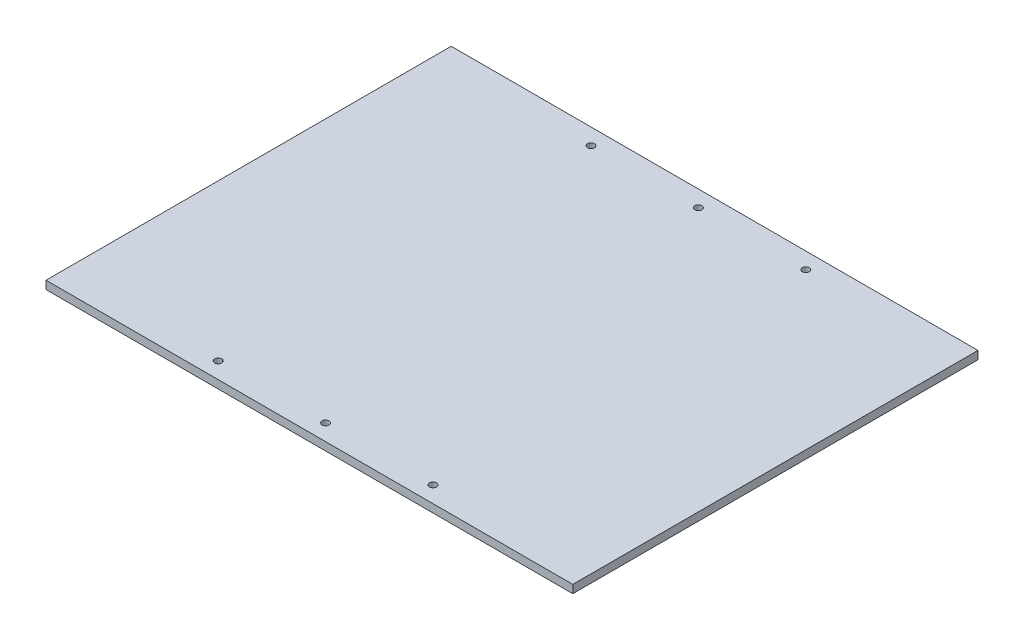
SolidWorks part; units mm, degrees
ref_plane "Ebene vorne" through (0, 0, 0) normal (0, 0, 1) x (1, 0, 0)
ref_plane "Ebene oben" through (0, 0, 0) normal (0, 1, 0) x (1, 0, 0)
ref_plane "Ebene rechts" through (0, 0, 0) normal (1, 0, 0) x (0, 0, -1)
sketch "Skizze1" plane through (0, 0, 0) normal (0, 1, 0) x (1, 0, 0)
  line L0 (-53, -92) -> (53, -92) construction
  line L1 (-130, -100) -> (130, -100)
  line L2 (-130, -100) -> (-130, 100)
  line L3 (-130, 100) -> (130, 100)
  line L4 (130, -100) -> (130, 100)
  line L5 (-130, -100) -> (130, 100) construction
  line L6 (-130, 100) -> (130, -100) construction
  line L7 (0, 0) -> (-130, 0) construction
  line L8 (130, 0) -> (0, 0) construction
  line L9 (0, 0) -> (0, 100) construction
  line L10 (0, 0) -> (0, -100) construction
  line L11 (-53, 92) -> (53, 92) construction
  circle A0 centre (-53, -92) radius 1.75
  circle A1 centre (53, -92) radius 1.75
  circle A2 centre (0, -92) radius 1.75
  circle A3 centre (0, 92) radius 1.75
  circle A4 centre (53, 92) radius 1.75
  circle A5 centre (-53, 92) radius 1.75
  point P0 (0, 0)
  dimension "D3" = 3.5
  dimension "D4" = 3.5
  dimension "D5" = 3.5
  dimension "D1" = 260
  dimension "D2" = 200
  dimension "D6" = 106
  dimension "D7" = 8
extrude "Aufsatz-Linear austragen1" add sketch "Skizze1" along normal blind 4
